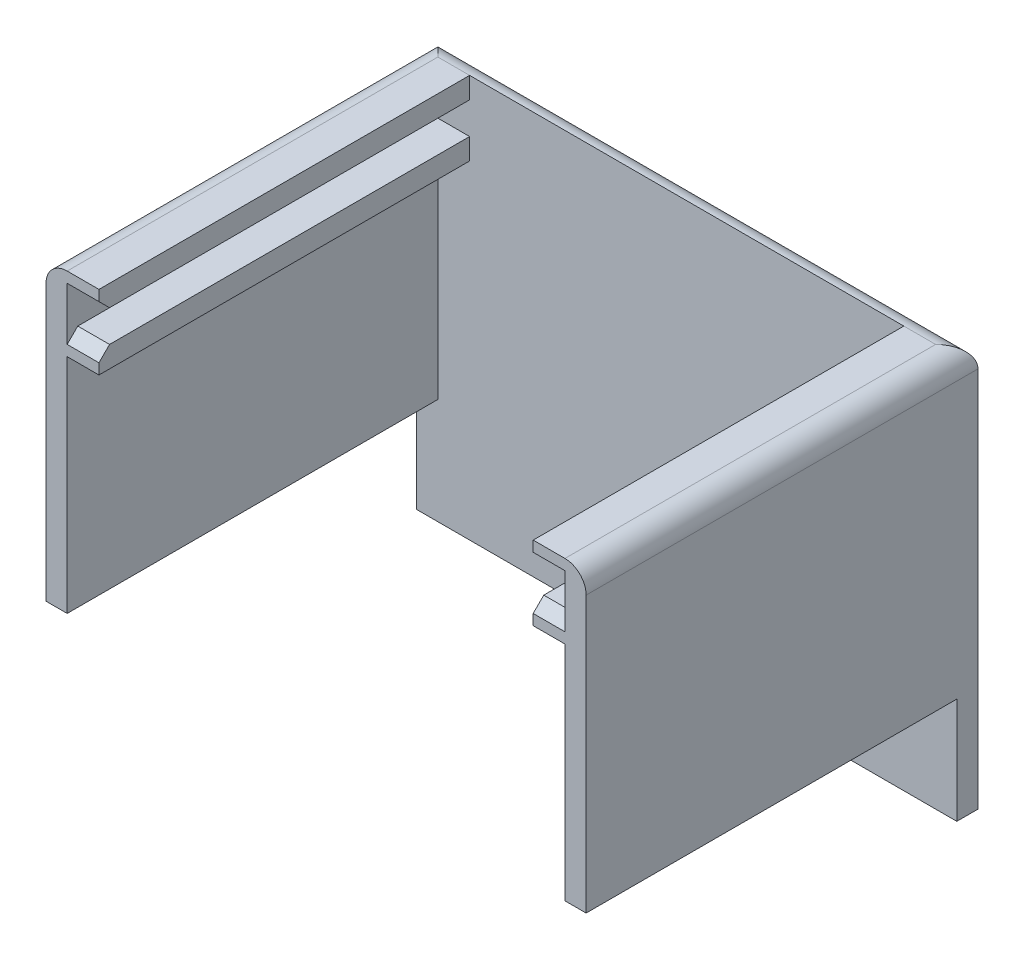
SolidWorks part; units mm, degrees
ref_plane "Alzado" through (0, 0, 0) normal (0, 0, 1) x (1, 0, 0)
ref_plane "Planta" through (0, 0, 0) normal (0, 1, 0) x (1, 0, 0)
ref_plane "Vista lateral" through (0, 0, 0) normal (1, 0, 0) x (0, 0, -1)
sketch "Croquis1" plane through (0, 0, 0) normal (0, 1, 0) x (1, 0, 0)
  line L0 (25.5, 19.5) -> (-25.5, 19.5)
  line L1 (23.5, 17.5) -> (-23.5, 17.5)
  line L2 (23.5, 17.5) -> (23.5, -17.5)
  line L3 (23.5, -17.5) -> (-23.5, -17.5)
  line L4 (-23.5, 17.5) -> (-23.5, -17.5)
  line L5 (23.5, 17.5) -> (-23.5, -17.5) construction
  line L6 (23.5, -17.5) -> (-23.5, 17.5) construction
  line L7 (-25.5, 19.5) -> (-25.5, -19.5)
  line L8 (25.5, -19.5) -> (-25.5, -19.5)
  line L9 (25.5, 19.5) -> (25.5, -19.5)
  point P0 (0, 0)
  dimension "D1" = 47
  dimension "D2" = 35
  dimension "D3" = 2
extrude "Saliente-Extruir1" add sketch "Croquis1" along normal blind 36
sketch "Croquis2" plane through (0, 0, 0) normal (0, -1, 0) x (1, 0, 0)
  line L1 (-25.5, -19.5) -> (25.5, -19.5)
  line L2 (-25.5, -19.5) -> (-25.5, 19.5)
  line L3 (-25.5, 19.5) -> (25.5, 19.5)
  line L4 (25.5, -19.5) -> (25.5, 19.5)
  line L5 (-25.5, -19.5) -> (25.5, 19.5) construction
  line L6 (-25.5, 19.5) -> (25.5, -19.5) construction
  point P0 (0, 0)
extrude "Saliente-Extruir2" add sketch "Croquis2" along normal blind 2
sketch "Croquis3" plane through (0, 36, 0) normal (0, 1, 0) x (1, 0, 0)
  line L0 (-25.5, -19.5) -> (25.5, -19.5) construction
  line L1 (-25.5, 19.5) -> (-20.5, 19.5)
  line L2 (-25.5, 19.5) -> (-25.5, -19.5)
  line L3 (-25.5, -19.5) -> (-20.5, -19.5)
  line L4 (-20.5, 19.5) -> (-20.5, -19.5)
  line L5 (25.5, 19.5) -> (-25.5, 19.5) construction
  line L6 (25.5, -19.5) -> (20.5, -19.5)
  line L7 (25.5, -19.5) -> (25.5, 19.5)
  line L8 (25.5, 19.5) -> (20.5, 19.5)
  line L9 (20.5, -19.5) -> (20.5, 19.5)
  dimension "D1" = 5
  dimension "D2" = 5
extrude "Saliente-Extruir3" add sketch "Croquis3" against normal blind 2
sketch "Croquis4" plane through (0, 36, 0) normal (0, 1, 0) x (1, 0, 0)
  line L0 (25.5, -19.5) -> (25.5, 19.5) construction
  line L1 (-25.5, -19.5) -> (25.5, -19.5)
  line L2 (-25.5, -19.5) -> (-25.5, -17.5)
  line L3 (-25.5, -17.5) -> (25.5, -17.5)
  line L4 (25.5, -19.5) -> (25.5, -17.5)
  dimension "D1" = 2
extrude "Cortar-Extruir1" cut sketch "Croquis4" against normal through all
sketch "Croquis5" plane through (0, 0, 17.5) normal (0, 0, 1) x (1, 0, 0)
  line L0 (-23.5, 34) -> (-23.5, 0) construction
  line L1 (-23.5, 31) -> (-20.5, 31)
  line L2 (-23.5, 31) -> (-23.5, 29)
  line L3 (-23.5, 29) -> (-20.5, 29)
  line L4 (-20.5, 31) -> (-20.5, 29)
  line L5 (-20.5, 31) -> (20.5, 31) construction
  line L6 (20.5, 31) -> (20.5, 34) construction
  line L7 (23.5, 34) -> (23.5, 0) construction
  line L8 (20.5, 31) -> (23.5, 31)
  line L9 (20.5, 31) -> (20.5, 29)
  line L10 (20.5, 29) -> (23.5, 29)
  line L11 (23.5, 31) -> (23.5, 29)
  dimension "D1" = 2
  dimension "D2" = 3
  dimension "D3" = 3
  dimension "D4" = 3
  dimension "D5" = 2
extrude "Saliente-Extruir4" add sketch "Croquis5" against normal up to surface (35 mm away) up to face at (0, 26, -17.5)
fillet "Redondeo1" radius 2 3 edges at (25.5, 36, -1) (0, 36, -19.5) (-25.5, 36, -1)
chamfer "Chaflán1" distance 1 angle 45 4 edges at (22, 31, 17.5) (22, 34, 17.5) (-22, 31, 17.5) (-22, 34, 17.5)
sketch "Croquis6" plane through (25.5, 0, 0) normal (1, 0, 0) x (0, 0, -1)
  line L0 (19.5, 34) -> (19.5, -2) construction
  line L1 (-17.5, -2) -> (17.5, -2)
  line L2 (-17.5, -2) -> (-17.5, 8)
  line L3 (-17.5, 8) -> (17.5, 8)
  line L4 (17.5, -2) -> (17.5, 8)
  dimension "D1" = 10
  dimension "D2" = 2
extrude "Cortar-Extruir2" cut sketch "Croquis6" against normal through all
